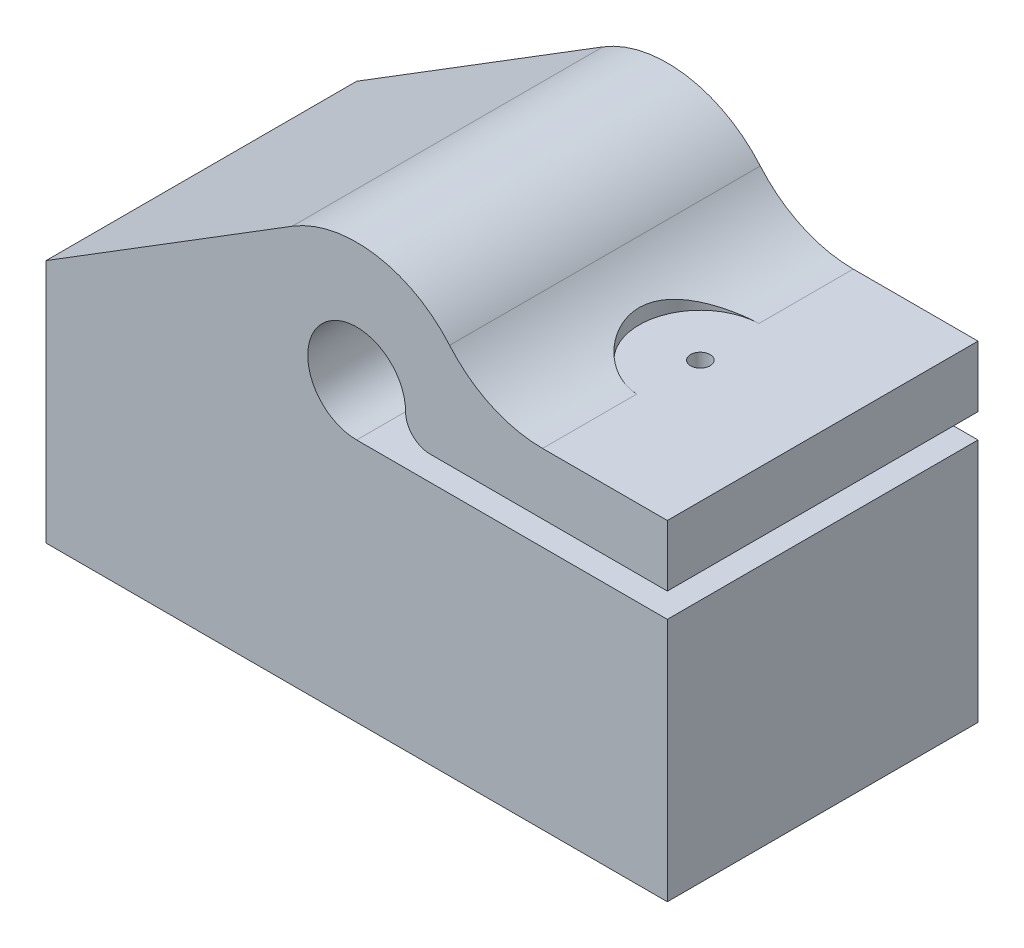
SolidWorks part; units mm, degrees
ref_plane "Front Plane" through (0, 0, 0) normal (0, 0, 1) x (1, 0, 0)
ref_plane "Top Plane" through (0, 0, 0) normal (0, 1, 0) x (1, 0, 0)
ref_plane "Right Plane" through (0, 0, 0) normal (1, 0, 0) x (0, 0, -1)
sketch "Sketch1" plane through (0, 0, 0) normal (0, 1, 0) x (1, 0, 0)
  line L1 (-25.4, -12.7) -> (25.4, -12.7)
  line L2 (-25.4, -12.7) -> (-25.4, 12.7)
  line L3 (-25.4, 12.7) -> (25.4, 12.7)
  line L4 (25.4, -12.7) -> (25.4, 12.7)
  line L5 (-25.4, -12.7) -> (25.4, 12.7) construction
  line L6 (-25.4, 12.7) -> (25.4, -12.7) construction
  point P0 (0, 0)
  dimension "D1" = 50.8
  dimension "D2" = 25.4
extrude "Boss-Extrude1" add sketch "Sketch1" along normal blind 20
sketch "Sketch2" plane through (0, 0, 12.7) normal (0, 0, 1) x (1, 0, 0)
  line L0 (-25.4, 20) -> (25.4, 20) construction
  line L1 (25.4, 22) -> (3.4641, 22)
  line L2 (25.4, 22) -> (25.4, 27)
  line L3 (25.4, 27) -> (9.5394, 27)
  line L4 (-25.4, 20) -> (-5.2749, 32.4956)
  line L5 (25.4, 20) -> (25.4, 0) construction
  circle A0 centre (0, 24) radius 4
  arc A1 (9.5394, 27) -> (-5.2749, 32.4956) centre (0, 24) ccw
  line M7 (25.4, 20) -> (-25.4, 20)
  dimension "D1" = 8
  dimension "D4" = 10
  dimension "D2" = 5
  dimension "D3" = 2
extrude "Boss-Extrude2" add sketch "Sketch2" against normal through all contours L3 A1 L4 A0 L1 L2 M7 region at (14.4321, 22.5269, 12.7)
fillet "Fillet1" radius 10 1 edges at (9.5394, 27, 0)
fillet "Fillet2" radius 2 1 edges at (3.4641, 22, 0)
sketch "Sketch3" plane through (0, 27, 0) normal (0, 1, 0) x (1, 0, 0)
  line L0 (25.4, 12.7) -> (25.4, -12.7) construction
  circle A0 centre (15.4, 0) radius 5
  point P0 (15.4, 0)
  dimension "D2" = 10
  dimension "D1" = 10
extrude "Cut-Extrude1" cut sketch "Sketch3" along normal through all
hole_wizard "Tap Drill for M2x0.4 Tap1" positions "Sketch4" profile "Sketch5" hole size "M2x0.4" standard "ANSI Metric" end condition through all
sketch "Sketch4" plane through (0, 27, 0) normal (0, 1, 0) x (1, 0, 0)
  point P0 (15.4, 0)
sketch "Sketch5" plane through (15.4, 27, 0) normal (1, 0, 0) x (0, 0, 1)
  line L0 (0, 0) -> (0, 27)
  line L1 (0, 27) -> (0.8, 27)
  line L2 (0.8, 27) -> (0.8, 0)
  line L5 (0.8, 0) -> (0, 0)
  line L11 (0, -6.35) -> (0, 107.95) construction
  dimension "Thru Hole Dia." = 1.6
  dimension "Thru Hole Depth" = 27
